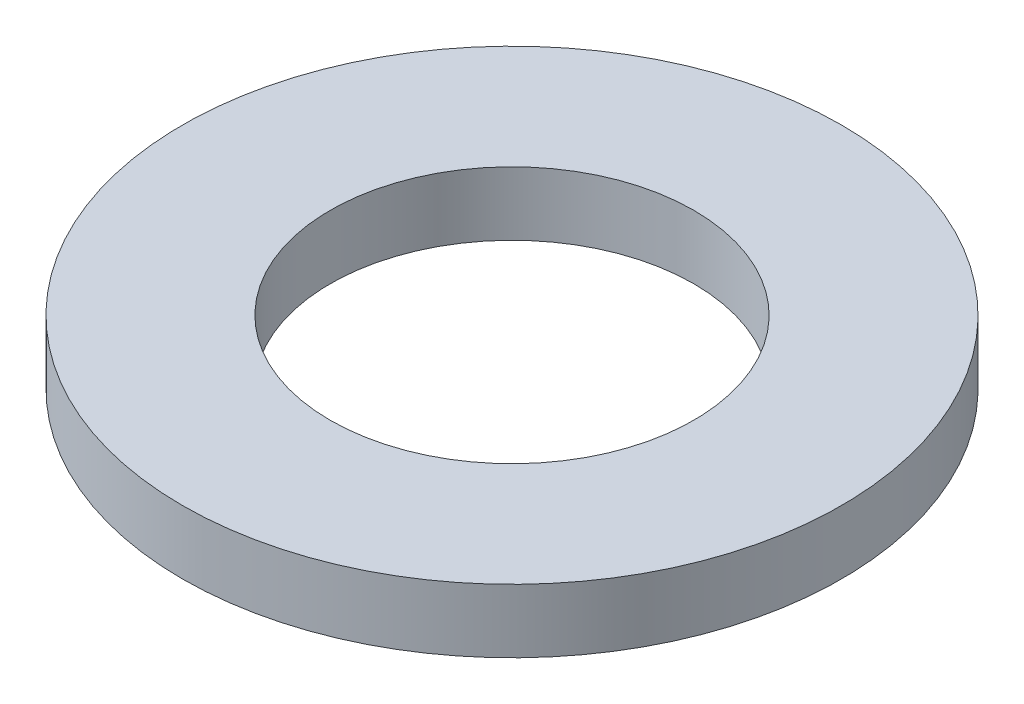
SolidWorks part; units mm, degrees
ref_plane "Front Plane" through (0, 0, 0) normal (0, 0, 1) x (1, 0, 0)
ref_plane "Top Plane" through (0, 0, 0) normal (0, 1, 0) x (1, 0, 0)
ref_plane "Right Plane" through (0, 0, 0) normal (1, 0, 0) x (0, 0, -1)
sketch "Sketch1" plane through (0, 0, 0) normal (0, 1, 0) x (1, 0, 0)
  circle A0 centre (0, 0) radius 72.5
  dimension "FLANGE_OD" = 145
extrude "Boss-Extrude1" add sketch "Sketch1" along normal blind 14
sketch "Sketch2" plane through (0, 0, 0) normal (0, 1, 0) x (1, 0, 0)
  circle A0 centre (0, 0) radius 40
  dimension "BORE_D" = 80
extrude "Cut-Extrude1" cut sketch "Sketch2" along normal through all
sketch "Sketch3" plane through (0, 14, 0) normal (0, 1, 0) x (1, 0, 0)
  circle A0 centre (0, 0) radius 33.3415 construction
  circle A1 centre (-33.3415, 0) radius 2.1036
  dimension "BOLT_D" = 4.2072
  dimension "BOLT_PCD" = 66.683
extrude "Cut-Extrude2" cut sketch "Sketch3" against normal blind 10.5632 rebuild error yes
pattern_circular "CirPattern1" count 8 over 360 rebuild error yes
